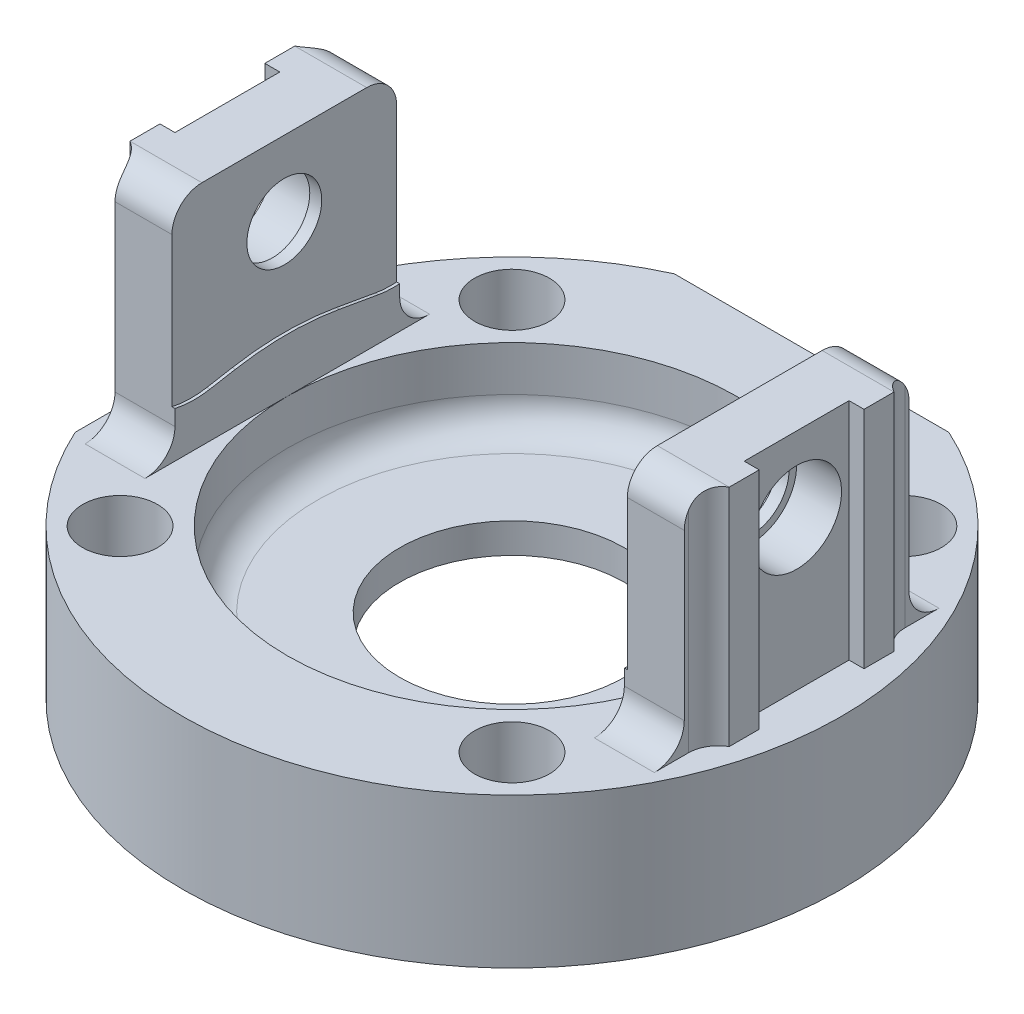
SolidWorks part; units mm, degrees
ref_plane "Front Plane" through (0, 0, 0) normal (0, 0, 1) x (1, 0, 0)
ref_plane "Top Plane" through (0, 0, 0) normal (0, 1, 0) x (1, 0, 0)
ref_plane "Right Plane" through (0, 0, 0) normal (1, 0, 0) x (0, 0, -1)
sketch "Sketch1" plane through (0, 0, 0) normal (0, 1, 0) x (1, 0, 0)
  circle A0 centre (0, 0) radius 22
  dimension "D1" = 44
extrude "Boss-Extrude1" add sketch "Sketch1" along normal blind 10
ref_plane "Plane1" through (0, 0, 0) normal (0, 1, 0) x (1, 0, 0)
sketch "Sketch5" plane through (0, 10, 0) normal (0, 1, 0) x (1, 0, 0)
  circle A0 centre (0, 0) radius 15
  dimension "D1" = 30
extrude "Cut-Extrude3" cut sketch "Sketch5" against normal blind 5
sketch "Sketch6" plane through (0, 10, 0) normal (0, 1, 0) x (1, 0, 0)
  line L0 (0, 0) -> (0, 8.4734)
  line L1 (0, -55) -> (0, 55) construction
  line L2 (0, 0) -> (-5.5218, 5.5218) construction
  circle A4 centre (-13.0815, 13.0815) radius 2.5
  circle A5 centre (13.0815, 13.0815) radius 2.5
  circle A6 centre (13.0815, -13.0815) radius 2.5
  circle A7 centre (-13.0815, -13.0815) radius 2.5
  point P12 (0, 0)
  point P20 (0, 0)
  dimension "D2" = 5
  dimension "D3" = 18.5
  dimension "D1" = 0
  dimension "D4" = 4
sketch "Sketch7" plane through (0, 0, 0) normal (0, -1, 0) x (-1, 0, 0)
  circle A0 centre (0, 0) radius 15
  dimension "D1" = 30
extrude "Cut-Extrude5" cut sketch "Sketch7" against normal blind 3
sketch "Sketch8" plane through (0, 3, 0) normal (0, -1, 0) x (-1, 0, 0)
  circle A0 centre (0, 0) radius 7.5
  dimension "D1" = 15
extrude "Cut-Extrude6" cut sketch "Sketch8" against normal blind 3
extrude "Cut-Extrude7" cut sketch "Sketch6" against normal blind 10 contours A5 | L2 A4 | A4 L2 | A7 | A6 L2 | L2 A6
sketch "Sketch9" plane through (0, 10, 0) normal (0, 1, 0) x (1, 0, 0)
  line L1 (-20, 14.6899) -> (-26.8336, 14.6899)
  line L2 (-20, 14.6899) -> (-20, -26.0082)
  line L3 (-20, -26.0082) -> (-26.8336, -26.0082)
  line L4 (-26.8336, 14.6899) -> (-26.8336, -26.0082)
  line L5 (-13.551, 26.1047) -> (12.5384, 26.1047)
  line L6 (-13.551, 26.1047) -> (-13.551, 20)
  line L7 (-13.551, 20) -> (12.5384, 20)
  line L8 (12.5384, 26.1047) -> (12.5384, 20)
  dimension "D1" = 20
  dimension "D2" = 20
extrude "Cut-Extrude8" cut sketch "Sketch9" against normal blind 10
sketch "Sketch10" plane through (0, 10, 0) normal (0, 1, 0) x (1, 0, 0)
  line L0 (-20, -9.1652) -> (-20, 9.1652) construction
  line L1 (-15, 15) -> (15, 15) construction
  line L2 (-15, 15) -> (-15, -15) construction
  line L3 (-15, -15) -> (15, -15) construction
  line L4 (15, 15) -> (15, -15) construction
  line L5 (-15, 15) -> (15, -15) construction
  line L6 (-15, -15) -> (15, 15) construction
  line L7 (-15, 7.5) -> (-19, 7.5)
  line L8 (-15, 7.5) -> (-15, -7.5)
  line L9 (-15, -7.5) -> (-19, -7.5)
  line L10 (-19, 7.5) -> (-19, -7.5)
  line L11 (-19, 5.5) -> (-20, 5.5)
  line L12 (-19, 5.5) -> (-19, 3.5)
  line L13 (-19, 3.5) -> (-20, 3.5)
  line L14 (-20, 5.5) -> (-20, 3.5)
  line L15 (0, -5.5) -> (0, 5.5) construction
  line L16 (-19, -3.5) -> (-20, -3.5)
  line L17 (-19, -3.5) -> (-19, -5.5)
  line L18 (-19, -5.5) -> (-20, -5.5)
  line L19 (-20, -3.5) -> (-20, -5.5)
  line L20 (20, -3.5) -> (20, -5.5)
  line L21 (19, -5.5) -> (20, -5.5)
  line L22 (19, -3.5) -> (19, -5.5)
  line L23 (19, -3.5) -> (20, -3.5)
  line L24 (20, 5.5) -> (20, 3.5)
  line L25 (19, 3.5) -> (20, 3.5)
  line L26 (19, 5.5) -> (19, 3.5)
  line L27 (19, 5.5) -> (20, 5.5)
  line L28 (19, 7.5) -> (19, -7.5)
  line L29 (15, -7.5) -> (19, -7.5)
  line L30 (15, 7.5) -> (15, -7.5)
  line L31 (15, 7.5) -> (19, 7.5)
  point P0 (0, 0)
  point P20 (-19.5, 5.5)
  line M7 (-20, 9.1652) -> (-20, -9.1652)
  dimension "D1" = 30
  dimension "D2" = 30
  dimension "D3" = 15
  dimension "D4" = 7.5
  dimension "D5" = 4
  dimension "D6" = 2
  dimension "D7" = 2
  dimension "D8" = 2
  dimension "D9" = 2
extrude "Boss-Extrude3" add sketch "Sketch10" along normal blind 15 contours L7 L10 L9 L8 | L13 L10 L11 M7 | L18 L10 L16 M7 | L31 L30 L29 L28 L22 L26 | L27 L26 L25 L24
fillet "Fillet1" radius 2 8 edges at (-17, 10, -7.5) (-17, 25, -7.5) (-17, 10, 7.5) (-17, 25, 7.5) (17, 10, -7.5) (17, 10, 7.5) (17, 25, -7.5) (17, 25, 7.5)
fillet "Fillet2" radius 10 3 edges at (-19, 10, 0) (-19.5, 10, 3.5) (-19.5, 10, -3.5)
sketch "Sketch11" plane through (-15, 0, 0) normal (1, 0, 0) x (0, 0, -1)
  line L0 (5.5, 25) -> (-5.5, 25) construction
  line L1 (-7.5, 23) -> (-7.5, 12) construction
  circle A0 centre (0, 20) radius 3
  dimension "D3" = 6
  dimension "D1" = 5
  dimension "D2" = 7.5
extrude "Cut-Extrude9" cut sketch "Sketch11" against normal blind 15 and the other way blind 42
fillet "Fillet3" radius 2 8 edges at (19, 17.5, 5.5) (19, 17.5, -5.5) (19.5, 10, -5.5) (19.5, 10, 5.5) (-19.5, 10, -5.5) (-19, 17.5, -5.5) (-19, 17.5, 5.5) (-19.5, 10, 5.5)
fillet "Fillet4" radius 2 2 edges at (0, 3, -15) (0, 5, 15)
sketch "Sketch13" plane through (15, 0, 0) normal (-1, 0, 0) x (0, 0, 1)
  line L0 (0, 20) -> (-7.1088, 18.7465)
  line L1 (0, 20) -> (6.2047, 18.9059)
  line L2 (0, 20) -> (-5.4012, 20) construction
  line L3 (0, 20) -> (-7.1088, 18.7465) construction
  line L4 (1.0419, 14.0912) -> (-6.0669, 12.8377)
  line L5 (-1.0419, 25.9088) -> (-8.1507, 24.6554)
  line L6 (0, 20) -> (6.2047, 18.9059) construction
  line L7 (1.0419, 25.9088) -> (7.2466, 24.8148)
  line L8 (-1.0419, 14.0912) -> (5.1628, 12.9971)
  arc A0 (1.0419, 14.0912) -> (-1.0419, 25.9088) centre (0, 20) ccw
  arc A1 (-8.1507, 24.6554) -> (-6.0669, 12.8377) centre (-7.1088, 18.7465) ccw
  arc A2 (1.0419, 25.9088) -> (-1.0419, 14.0912) centre (0, 20) ccw
  arc A3 (5.1628, 12.9971) -> (7.2466, 24.8148) centre (6.2047, 18.9059) ccw
  point P3 (-3.5544, 19.3733)
  point P10 (3.1024, 19.453)
  dimension "D3" = 6
  dimension "D4" = 6
  dimension "D1" = 10
  dimension "D2" = 10
extrude "Cut-Extrude18" cut sketch "Sketch13" against normal blind 0.2 and the other way blind 30.2
fillet "Fillet5" radius 20 2 edges at (-15.1, 13.9074, 0) (15.1, 13.9074, 0)
sketch "Sketch14" plane through (15.2, 0, 0) normal (-1, 0, 0) x (0, 0, 1)
  circle A0 centre (0, 20) radius 3
  circle A1 centre (0, 20) radius 2.5
  dimension "D1" = 5
extrude "Boss-Extrude4" add sketch "Sketch14" against normal blind 0.8
sketch "Sketch15" plane through (-15.2, 0, 0) normal (1, 0, 0) x (0, 0, -1)
  circle A0 centre (0, 20) radius 3
  circle A1 centre (0, 20) radius 2.5
  dimension "D1" = 5
extrude "Boss-Extrude5" add sketch "Sketch15" against normal blind 0.8
sketch "Sketch17" plane through (0, 0, -20) normal (0, 0, -1) x (-1, 0, 0)
  line L0 (23.1, 0) -> (-23.1, 0) construction
  line L1 (9.1652, 0) -> (-9.1652, 0) construction
  circle A0 centre (-5, 5) radius 2.5
  circle A1 centre (5, 5) radius 2.5
  dimension "D5" = 5
  dimension "D6" = 5
  dimension "D1" = 10
  dimension "D2" = 5
  dimension "D3" = 5
  dimension "D4" = 5
extrude "Cut-Extrude20" cut sketch "Sketch17" against normal blind 4
sketch "Sketch18" plane through (-20, 0, 0) normal (-1, 0, 0) x (0, 0, 1)
  line L1 (23.1, 0) -> (-23.1, 0) construction
  line L2 (9.1652, 0) -> (-9.1652, 0) construction
  circle A0 centre (-5, 5) radius 2.5
  circle A1 centre (5, 5) radius 2.5
  dimension "D1" = 5
  dimension "D3" = 5
  dimension "D4" = 5
  dimension "D2" = 5
  dimension "D5" = 5
  dimension "D6" = 5
extrude "Cut-Extrude21" cut sketch "Sketch18" against normal blind 4
